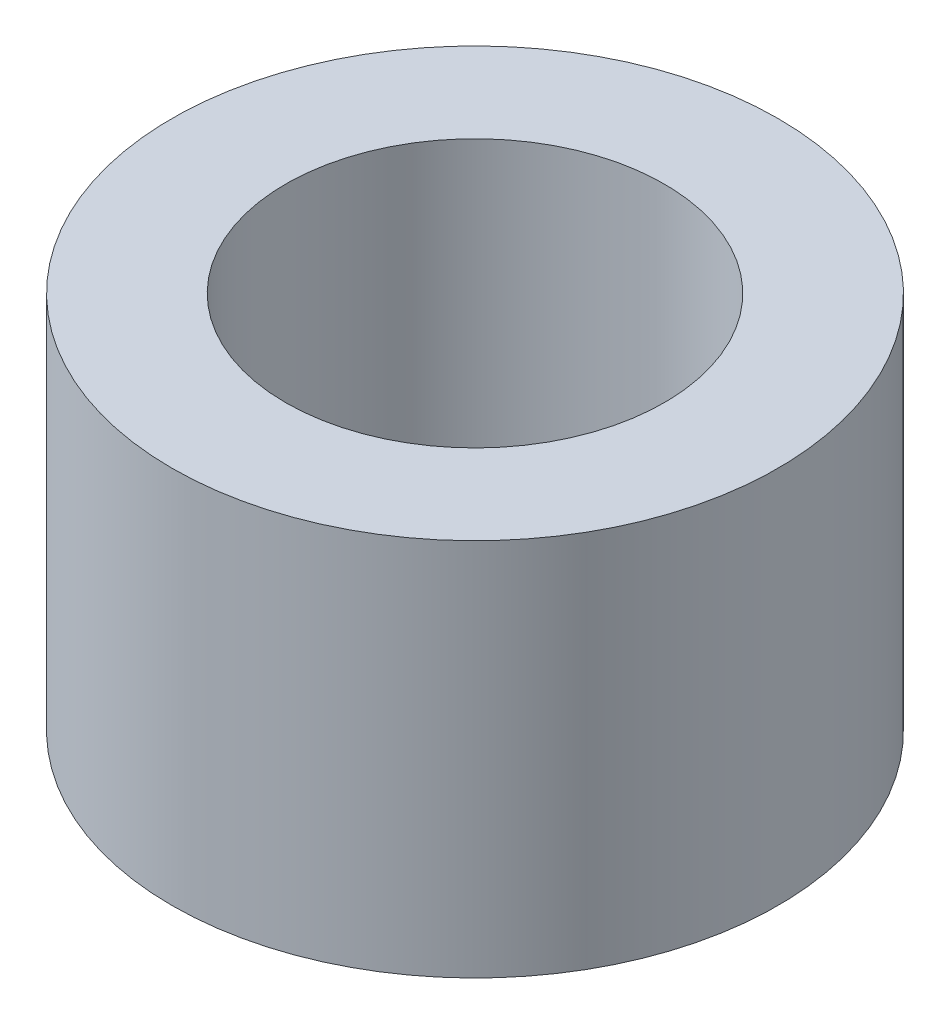
SolidWorks part; units mm, degrees
ref_plane "Front Plane" through (0, 0, 0) normal (0, 0, 1) x (1, 0, 0)
ref_plane "Top Plane" through (0, 0, 0) normal (0, 1, 0) x (1, 0, 0)
ref_plane "Right Plane" through (0, 0, 0) normal (1, 0, 0) x (0, 0, -1)
sketch "Sketch1" plane through (0, 0, 0) normal (0, 1, 0) x (1, 0, 0)
  circle A0 centre (0, 0) radius 6.35
  circle A1 centre (0, 0) radius 3.9688
  dimension "D1" = 12.7
  dimension "D2" = 7.9375
extrude "Boss-Extrude1" add sketch "Sketch1" along normal blind 7.9375
